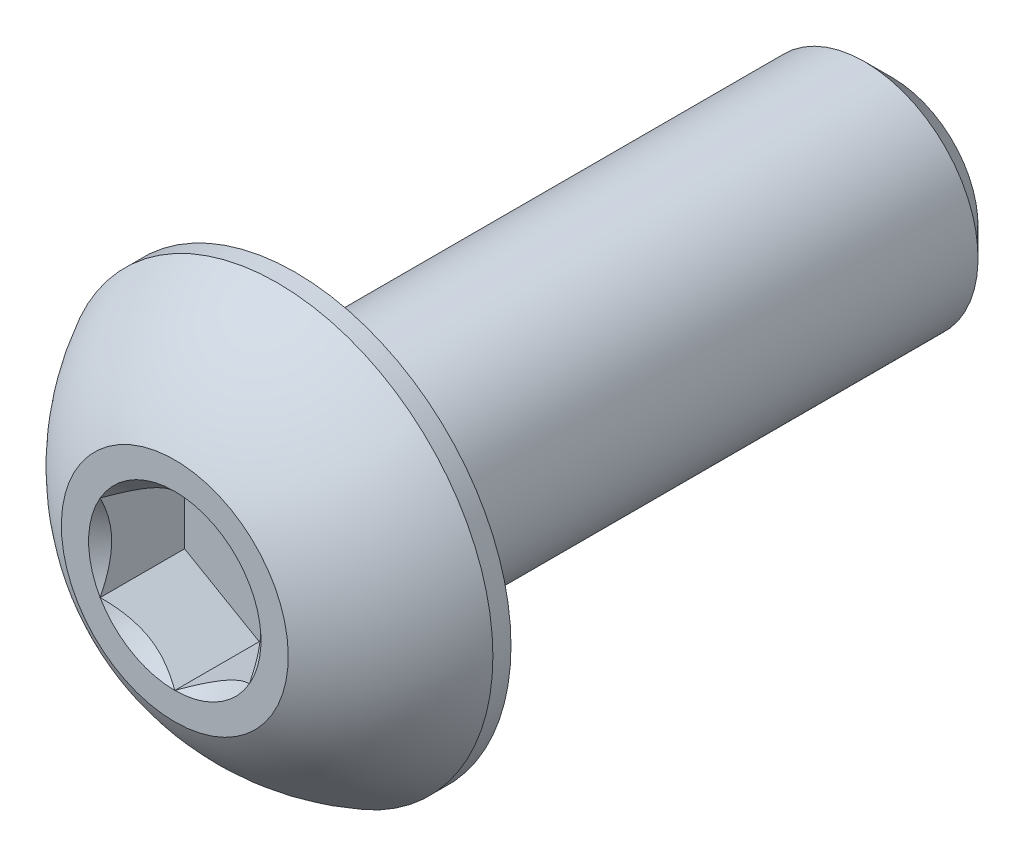
SolidWorks part; units mm, degrees
ref_plane "Front" through (0, 0, 0) normal (0, 0, 1) x (1, 0, 0)
ref_plane "Top" through (0, 0, 0) normal (0, 1, 0) x (1, 0, 0)
ref_plane "Right" through (0, 0, 0) normal (1, 0, 0) x (0, 0, -1)
sketch "Sketch1" plane through (0, 0, 0) normal (1, 0, 0) x (0, 0, -1)
  line L2 (2.5654, 2.413) -> (15.2654, 2.413)
  line L3 (15.2654, 2.413) -> (15.2654, 0)
  line L4 (15.2654, 0) -> (2.5654, 0)
  line L6 (2.1806, 4.5847) -> (2.5654, 4.5847) construction
  line L7 (15.2654, 2.413) -> (15.2654, -2.413) construction
  line L8 (0, 0) -> (2.5654, 0) construction
  line L9 (2.5654, 4.5847) -> (2.5654, -4.5847) construction
  line L11 (2.5654, 2.413) -> (2.5654, 0)
  line L13 (0, 1.5875) -> (0, -1.5875) construction
  line L14 (0, 1.5875) -> (0, 2.413) construction
  arc A3 (0, 2.413) -> (2.1806, 4.5847) centre (4.5749, 0) cw construction
  dimension "D1" = 0.3848
revolve "Revolve1" add sketch "Sketch1" angle 360 mid plane about L4
sketch "Sketch3" plane through (0, 0, -15.2654) normal (0, 0, -1) x (-1, 0, 0)
  circle A0 centre (0, 0) radius 2.413
curve "Helix/Spiral1" pitch 0.7937 height 17.8054 turns 22.432
sketch "Sketch2" plane through (0, 0, 0) normal (1, 0, 0) x (0, 0, -1)
  line L0 (15.2654, 2.413) -> (15.9599, 2.413)
  line L1 (15.9599, 2.413) -> (15.6623, 1.8974)
  line L2 (15.6623, 1.8974) -> (15.5631, 1.8974)
  line L3 (15.5631, 1.8974) -> (15.2654, 2.413)
  line L4 (15.4142, 2.1552) -> (15.8111, 2.1552) construction
  dimension "D1" = 60
  dimension "D2" = 0.0992
  dimension "D3" = 0.3969
chamfer "Chamfer1" distance 0.5953 angle 45 1 edges at (0, 2.413, -15.2654)
sweep "Cut-Sweep1" [suppressed] cut profiles "Sketch2" path "Helix/Spiral1"
sketch "Sketch7" plane through (0, 0, 0) normal (1, 0, 0) x (0, 0, -1)
  line L6 (2.1806, 4.5847) -> (2.5654, 4.5847) construction
  line L8 (0, 0) -> (2.5654, 0) construction
  line L11 (2.5654, 4.5847) -> (2.5654, -4.5847) construction
  line L12 (2.1806, 4.5847) -> (2.5654, 4.5847)
  line L13 (0, 0) -> (2.5654, 0)
  line L14 (0, 1.5875) -> (0, -1.5875) construction
  line L15 (2.5654, 4.5847) -> (2.5654, 0)
  line L16 (0, 2.413) -> (0, 0)
  arc A2 (2.1806, 4.5847) -> (0, 2.413) centre (4.5749, 0) ccw construction
  arc A3 (2.1806, 4.5847) -> (0, 2.413) centre (4.5749, 0) ccw
revolve "Revolve2" add sketch "Sketch7" angle 360 mid plane about L13
sketch "Sketch5" plane through (0, 0, 0) normal (0, 0, 1) x (1, 0, 0)
  line L1 (1.5875, -0.9165) -> (1.5875, 0.9165)
  line L2 (1.5875, 0.9165) -> (0, 1.8331)
  line L3 (0, 1.8331) -> (-1.5875, 0.9165)
  line L4 (-1.5875, 0.9165) -> (-1.5875, -0.9165)
  line L5 (-1.5875, -0.9165) -> (0, -1.8331)
  line L6 (0, -1.8331) -> (1.5875, -0.9165)
  circle A0 centre (0, 0) radius 1.5875 construction
extrude "Cut-Extrude2" cut sketch "Sketch5" against normal blind 1.7958
sketch "Sketch6" plane through (0, 0, 0) normal (0, 0, 1) x (1, 0, 0)
  circle A0 centre (0, 0) radius 1.8331
extrude "Cut-Extrude3" cut sketch "Sketch6" against normal blind 1.7958 draft 45
sketch "Sketch9" [suppressed] plane through (0, 0, -2.5654) normal (0, 0, 1) x (1, 0, 0)
  circle A2 centre (0, 0) radius 2.413
extrude "Boss-Extrude2" [suppressed] add sketch "Sketch9" against normal offset from surface (28.575 mm away) 22.225
sketch "Sketch10" plane through (0, 0, 0) normal (1, 0, 0) x (0, 0, -1)
  line L0 (15.2654, 2.413) -> (15.2654, -2.413) construction
  point P0 (14.0748, -2.413)
  dimension "D1" = 1.1906
equation "\"D3@Helix/Spiral1\" = \"Lg@Sketch1\" + \"Head Ht@Sketch1\" + .1"
equation "\"D2@Sketch2\" = \"D4@Helix/Spiral1\" * .125"
equation "\"D3@Sketch2\" = \"D4@Helix/Spiral1\" * .5"
equation "\"D1@Chamfer1\" = \"D4@Helix/Spiral1\" * .75"
equation "\"D1@Cut-Extrude2\" = \"Head Ht@Sketch1\" * .7"
equation "\"D1@Sketch1\" = \"Head Ht@Sketch1\" * .15"
equation "\"D1@Sketch10\" = \"D4@Helix/Spiral1\" * 1.5"
equation "\"D1@Cut-Extrude3\" = \"D1@Cut-Extrude2\""
